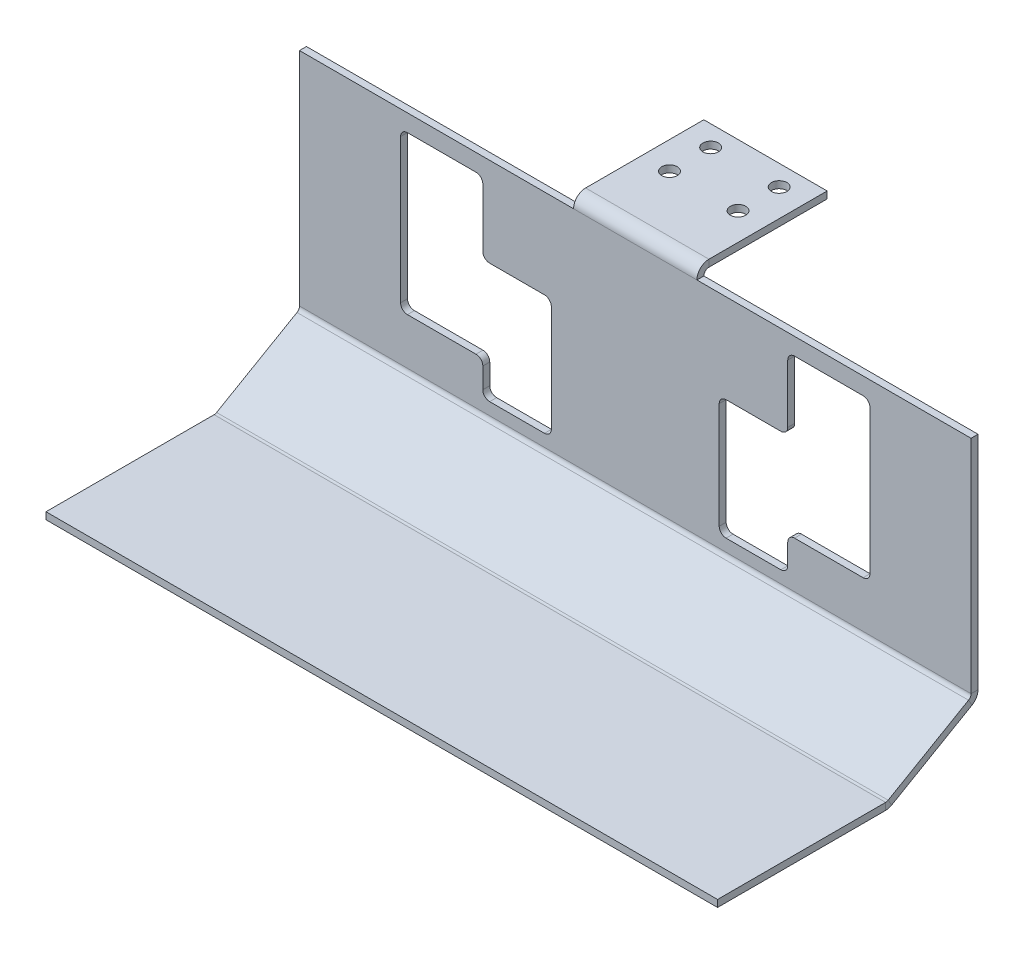
SolidWorks part; units mm, degrees
note: The reader was unsure of these and kept them because the rebuilt part matched: flange length of "Edge-Flange1", "Edge-Flange2", "Edge-Flange3".
ref_plane "Front Plane" through (0, 0, 0) normal (0, 0, 1) x (1, 0, 0)
ref_plane "Top Plane" through (0, 0, 0) normal (0, 1, 0) x (1, 0, 0)
ref_plane "Right Plane" through (0, 0, 0) normal (1, 0, 0) x (0, 0, -1)
sketch "Sketch1" plane through (0, 0, 0) normal (0, 0, 1) x (1, 0, 0)
  line L0 (49, 32.71) -> (49, 0) construction
  line L1 (0, 32.71) -> (98, 32.71)
  line L2 (0, 32.71) -> (0, 0)
  line L3 (0, 0) -> (98, 0)
  line L4 (98, 32.71) -> (98, 0)
  line L5 (61.25, 18.71) -> (61.25, 3.21)
  line L6 (70.25, 19.71) -> (62.25, 19.71)
  line L7 (25.75, 30.21) -> (15.75, 30.21)
  line L8 (26.75, 20.71) -> (26.75, 29.21)
  line L9 (15.75, 7.21) -> (25.75, 7.21)
  line L10 (14.75, 29.21) -> (14.75, 8.21)
  line L11 (70.25, 2.21) -> (62.25, 2.21)
  line L12 (71.25, 6.21) -> (71.25, 3.21)
  line L13 (83.25, 29.21) -> (83.25, 8.21)
  line L14 (82.25, 7.21) -> (72.25, 7.21)
  line L15 (26.75, 6.21) -> (26.75, 3.21)
  line L16 (27.75, 2.21) -> (35.75, 2.21)
  line L17 (71.25, 20.71) -> (71.25, 29.21)
  line L18 (72.25, 30.21) -> (82.25, 30.21)
  line L20 (27.75, 19.71) -> (35.75, 19.71)
  line L23 (36.75, 18.71) -> (36.75, 3.21)
  arc A0 (26.75, 29.21) -> (25.75, 30.21) centre (25.75, 29.21) ccw
  arc A1 (26.75, 20.71) -> (27.75, 19.71) centre (27.75, 20.71) ccw
  arc A2 (35.75, 19.71) -> (36.75, 18.71) centre (35.75, 18.71) cw
  arc A3 (36.75, 3.21) -> (35.75, 2.21) centre (35.75, 3.21) cw
  arc A4 (27.75, 2.21) -> (26.75, 3.21) centre (27.75, 3.21) cw
  arc A5 (26.75, 6.21) -> (25.75, 7.21) centre (25.75, 6.21) ccw
  arc A6 (15.75, 7.21) -> (14.75, 8.21) centre (15.75, 8.21) cw
  arc A7 (14.75, 29.21) -> (15.75, 30.21) centre (15.75, 29.21) cw
  arc A8 (83.25, 29.21) -> (82.25, 30.21) centre (82.25, 29.21) ccw
  arc A9 (82.25, 7.21) -> (83.25, 8.21) centre (82.25, 8.21) ccw
  arc A10 (71.25, 6.21) -> (72.25, 7.21) centre (72.25, 6.21) cw
  arc A11 (70.25, 2.21) -> (71.25, 3.21) centre (70.25, 3.21) ccw
  arc A12 (61.25, 3.21) -> (62.25, 2.21) centre (62.25, 3.21) ccw
  arc A13 (62.25, 19.71) -> (61.25, 18.71) centre (62.25, 18.71) ccw
  arc A14 (71.25, 20.71) -> (70.25, 19.71) centre (70.25, 20.71) cw
  arc A15 (71.25, 29.21) -> (72.25, 30.21) centre (72.25, 29.21) cw
  point P25 (26.75, 30.21)
  point P28 (26.75, 19.71)
  point P31 (36.75, 19.71)
  point P34 (36.75, 2.21)
  point P37 (26.75, 2.21)
  point P40 (26.75, 7.21)
  point P43 (14.75, 7.21)
  point P46 (14.75, 30.21)
  point P63 (83.25, 30.21)
  point P64 (83.25, 7.21)
  point P65 (71.25, 7.21)
  point P66 (71.25, 2.21)
  point P67 (61.25, 2.21)
  point P68 (61.25, 19.71)
  point P69 (71.25, 19.71)
  point P70 (71.25, 30.21)
  dimension "D10" = 1
  dimension "D11" = 1
  dimension "D1" = 32.71
  dimension "D2" = 98
  dimension "D3" = 2.5
  dimension "D4" = 14.75
  dimension "D5" = 23
  dimension "D6" = 12
  dimension "D7" = 10
  dimension "D8" = 17.5
  dimension "D9" = 5
base flange "Base-Flange1" sketch "Sketch1" thickness 1.016 reverse thickness direction no parameters "D1"=0.7366
edge flange "Edge-Flange1" sketch "Sketch8" flange angle 90 flange length 19 flange position bend outside bend radius 0.7366 thickness 1.016 relief rectangular parameters "D6"=10
sketch "Sketch8" plane through (0, 32.71, -1.016) normal (0, 1, 0) x (1, 0, 0)
  line L0 (98, 0) -> (0, 0) construction
  line L1 (58, 0) -> (40, 0)
  line L2 (40, 0) -> (40, 17.984)
  line L3 (40, 17.984) -> (58, 17.984)
  line L4 (58, 17.984) -> (58, 0)
  line L5 (49, 0) -> (49, -1.016) construction
  line L6 (98, -1.016) -> (0, -1.016) construction
  dimension "D1" = 18
bend "EdgeBend1" bend radius 0.7366 bend angle 90 parameters "D5"=1
edge flange "Edge-Flange2" sketch "Sketch11" flange angle 120 flange length 14.75 flange position material outside bend radius 0.7366 thickness 1.016 relief rectangular parameters "D6"=10
sketch "Sketch11" plane through (0, 0, 0) normal (0, -0.866, -0.5) x (1, 0, 0)
  line L0 (0, 0) -> (98, 0) construction
  line L1 (0, 0) -> (98, 0)
  line L2 (0, 0) -> (0, 14.1634)
  line L3 (0, 14.1634) -> (98, 14.1634)
  line L4 (98, 14.1634) -> (98, 0)
bend "EdgeBend2" bend radius 0.7366 bend angle 60 parameters "D5"=2
edge flange "Edge-Flange3" sketch "Sketch16" flange angle 150 flange length 25 flange position material outside bend radius 0.7366 thickness 1.016 relief rectangular parameters "D6"=10
sketch "Sketch16" plane through (0, -7.0817, 12.2659) normal (0, 1, 0) x (-1, 0, 0)
  line L2 (-98, 0) -> (-98, 24.7278)
  line L3 (-98, 24.7278) -> (0, 24.7278)
  line L4 (0, 24.7278) -> (0, 0)
  line L6 (0, 0) -> (-98, 0) construction
  line L7 (0, 0) -> (-98, 0)
bend "EdgeBend3" bend radius 0.7366 bend angle 30 parameters "D5"=3
sketch "Sketch17" plane through (0, 34.4626, 0) normal (0, 1, 0) x (1, 0, 0)
  line L1 (58, 19) -> (40, 19) construction
  line L2 (58, 1.7526) -> (40, 1.7526) construction
  line L3 (44, 19) -> (44, 1.7526) construction
  line L4 (54, 19) -> (54, 1.7526) construction
  line L5 (40, 16) -> (58, 16) construction
  line L6 (40, 19) -> (40, 1.7526) construction
  line L7 (58, 1.7526) -> (58, 19) construction
  line L8 (40, 10) -> (58, 10) construction
  circle A0 centre (54, 10) radius 1.1303
  circle A1 centre (54, 16) radius 1.1303
  circle A2 centre (44, 10) radius 1.1303
  circle A3 centre (44, 16) radius 1.1303
  dimension "D1" = 2.2606
  dimension "D2" = 3
  dimension "D3" = 6
  dimension "D4" = 4
  dimension "D5" = 4
extrude "Cut-Extrude1" cut sketch "Sketch17" against normal up to next normal cut yes
sketch "Bend-Lines1" [suppressed] plane through (0, 0, 0) normal (0, 1, 0) x (1, 0, 0)
sketch "Bounding-Box1" [suppressed] plane through (0, 0, 0) normal (0, 1, 0) x (1, 0, 0)
sheet metal parameters "Sheet-Metal1" thickness 1.016 parameters "D1"=0.7366
flat pattern "Flat-Pattern1" [suppressed]
sketch "Bend-Lines2" plane through (0, 0, 0) normal (0, 1, 0) x (1, 0, 0)
sketch "Bounding-Box2" [suppressed] plane through (0, 0, 0) normal (0, 1, 0) x (1, 0, 0)
sheet metal parameters "Sheet-Metal2" thickness 1.016 parameters "D1"=0.7366
flat pattern "Flat-Pattern1" [suppressed]
sketch "Bend-Lines2" plane through (0, 0, 0) normal (0, 1, 0) x (1, 0, 0)
sketch "Bounding-Box2" [suppressed] plane through (0, 0, 0) normal (0, 1, 0) x (1, 0, 0)
bend of the flat pattern "Flatten-<EdgeBend1>1"
sheet metal parameters "Sheet-Metal3" thickness 1.016 parameters "D1"=0.7366
flat pattern "Flat-Pattern1" [suppressed]
sketch "Bend-Lines2" plane through (0, 0, 0) normal (0, 1, 0) x (1, 0, 0)
sketch "Bounding-Box2" [suppressed] plane through (0, 0, 0) normal (0, 1, 0) x (1, 0, 0)
bend of the flat pattern "Flatten-<EdgeBend1>1"
bend of the flat pattern "Flatten-<EdgeBend2>1"
sheet metal parameters "Sheet-Metal4" thickness 1.016 parameters "D1"=0.7366
flat pattern "Flat-Pattern1" [suppressed]
sketch "Bend-Lines2" plane through (0, 0, 0) normal (0, 1, 0) x (1, 0, 0)
sketch "Bounding-Box2" [suppressed] plane through (0, 0, 0) normal (0, 1, 0) x (1, 0, 0)
bend of the flat pattern "Flatten-<EdgeBend1>1"
bend of the flat pattern "Flatten-<EdgeBend2>1"
bend of the flat pattern "Flatten-<EdgeBend3>1"
sheet metal parameters "Sheet-Metal5" thickness 1.016 parameters "D1"=0.7366
flat pattern "Flat-Pattern1"
sketch "Bend-Lines2" plane through (0, 0, 0) normal (0, 0, 1) x (1, 0, 0)
  line L0 (0, -14.7447) -> (98, -14.7447) construction
  line L1 (0, -0.2264) -> (98, -0.2264) construction
  line L2 (58, 33.6875) -> (40, 33.6875) construction
  line L3 (0, -14.7447) -> (98, -14.7447) construction
  line L4 (0, -0.2264) -> (98, -0.2264) construction
  line L5 (58, 33.6875) -> (40, 33.6875) construction
sketch3d "Bounding-Box2" [suppressed]
  line L0 (0, -39.6009, 0) -> (98, -39.6009, 0) construction
  line L1 (0, 51.9124, 0) -> (98, 51.9124, 0) construction
  line L2 (0, -39.6009, 0) -> (0, 51.9124, 0) construction
  line L3 (98, -39.6009, 0) -> (98, 51.9124, 0) construction
bend of the flat pattern "Flatten-<EdgeBend1>1"
bend of the flat pattern "Flatten-<EdgeBend2>1"
bend of the flat pattern "Flatten-<EdgeBend3>1"
